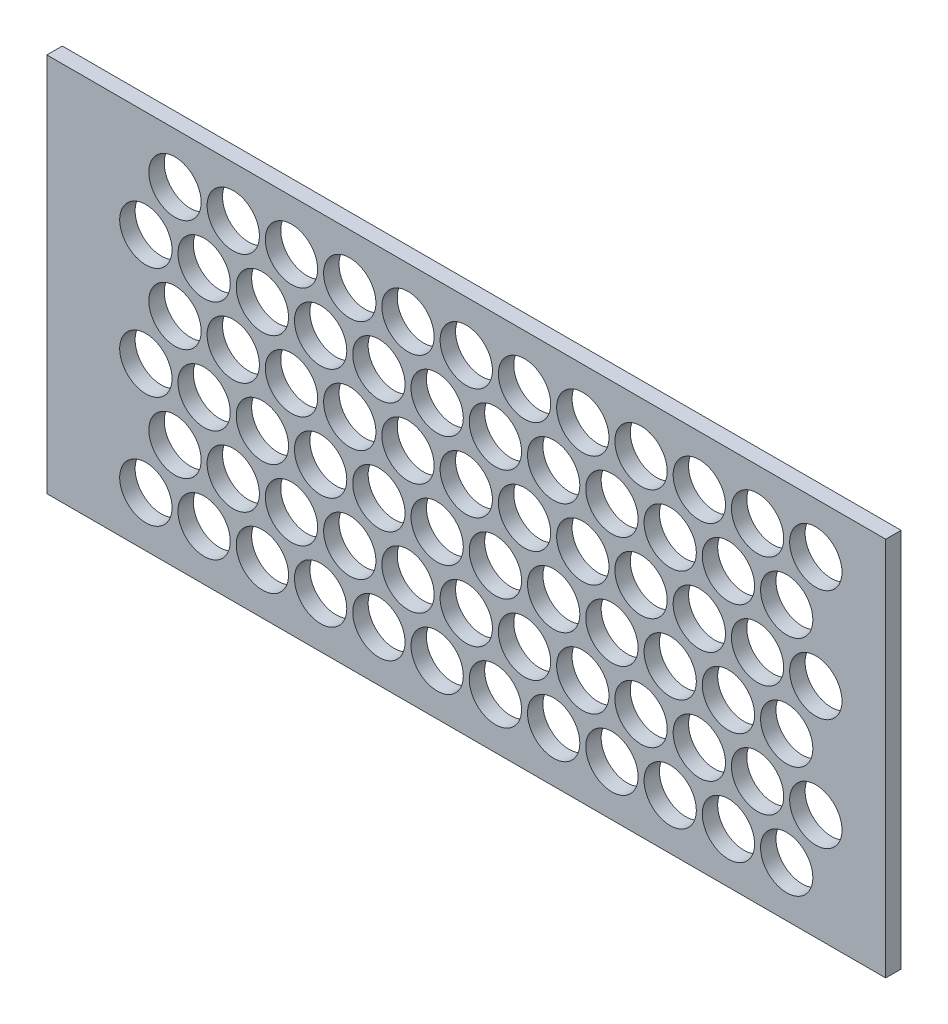
SolidWorks part; units mm, degrees
material "Custom Plastic"
ref_plane "X-Y Datum" through (0, 0, 0) normal (0, 0, 1) x (1, 0, 0)
ref_plane "X-Z Datum" through (0, 0, 0) normal (0, 1, 0) x (1, 0, 0)
ref_plane "Y-Z Datum" through (0, 0, 0) normal (1, 0, 0) x (0, 0, -1)
sketch "Sketch1" plane through (0, 0, 0) normal (0, 0, 1) x (1, 0, 0)
  line L0 (20, 167.2119) -> (0, 167.2119)
  line L2 (0, 10.6619) -> (0, 167.2119)
  line L6 (337.55, 167.2119) -> (345.57, 167.2119)
  line L11 (337.55, 167.2119) -> (337.55, 10.6619)
  line L13 (20, 167.2119) -> (20, 10.6619)
  line L16 (20, 167.2119) -> (337.55, 167.2119)
  line L17 (20, 10.6619) -> (0, 10.6619)
  line L18 (30, 157.2119) -> (327.55, 157.2119)
  line L19 (30, 157.2119) -> (30, 20.6619)
  line L20 (30, 20.6619) -> (327.55, 20.6619)
  line L21 (327.55, 157.2119) -> (327.55, 20.6619)
  line L22 (20, 167.2119) -> (20, 10.6619)
  line L23 (20, 10.6619) -> (337.55, 10.6619)
  line L24 (337.55, 167.2119) -> (337.55, 10.6619)
  line L25 (345.57, 167.2119) -> (345.57, 10.6619)
  line L26 (345.57, 10.6619) -> (337.55, 10.6619)
  circle A0 centre (40.7752, 31.4369) radius 10.775
  circle A1 centre (64.7752, 31.4369) radius 10.775
  circle A2 centre (52.7752, 54.4369) radius 10.775
  dimension "D1" = 20
  dimension "D4" = 10
  dimension "D6" = 21.55
  dimension "D2" = 297.55
  dimension "D3" = 156.55
  dimension "D5" = 10
  dimension "D7" = 23
  dimension "D8" = 12
  dimension "D9" = 24
  dimension "D10" = 10
  dimension "D11" = 10
  dimension "D12" = 136.55
  dimension "D13" = 8.02
extrude "Boss-Extrude1" add sketch "Sketch1" along normal blind 6.35 contours L20 A1 L21 L18 L19 A0 A2 | A2 | A1 | L13 L18 L21 L20 L19 | L2 L13 | A0 L19 L20 | L26 L25 L6 L11 | A0 region at (10, 88.9369, 0) region at (178.775, 163.6715, 0) region at (341.56, 88.9369, 0) region at (64.7752, 31.4369, 0) region at (182.2622, 90.3161, 0) region at (52.7752, 54.4369, 0)
sketch "Sketch2" plane through (0, 0, 6.35) normal (0, 0, 1) x (1, 0, 0)
  line L1 (30, 157.2119) -> (327.55, 157.2119)
  line L2 (30, 157.2119) -> (30, 20.6619)
  line L3 (30, 20.6619) -> (327.55, 20.6619)
  line L4 (327.55, 157.2119) -> (327.55, 20.6619)
  circle A0 centre (40.7752, 31.4369) radius 10.775
  circle A1 centre (52.7752, 54.4369) radius 10.775
extrude "Cut-Extrude1" cut sketch "Sketch2" against normal blind 6.35 contours A1 | A0 region at (40.7752, 31.4369, 6.35) region at (52.7752, 54.4369, 6.35)
pattern_linear "LPattern1" count 12 spacing 24 along (1, 0, 0) of "Cut-Extrude1"
pattern_linear "LPattern2" count 3 spacing 46 along (0, 1, 0) of "LPattern1"
